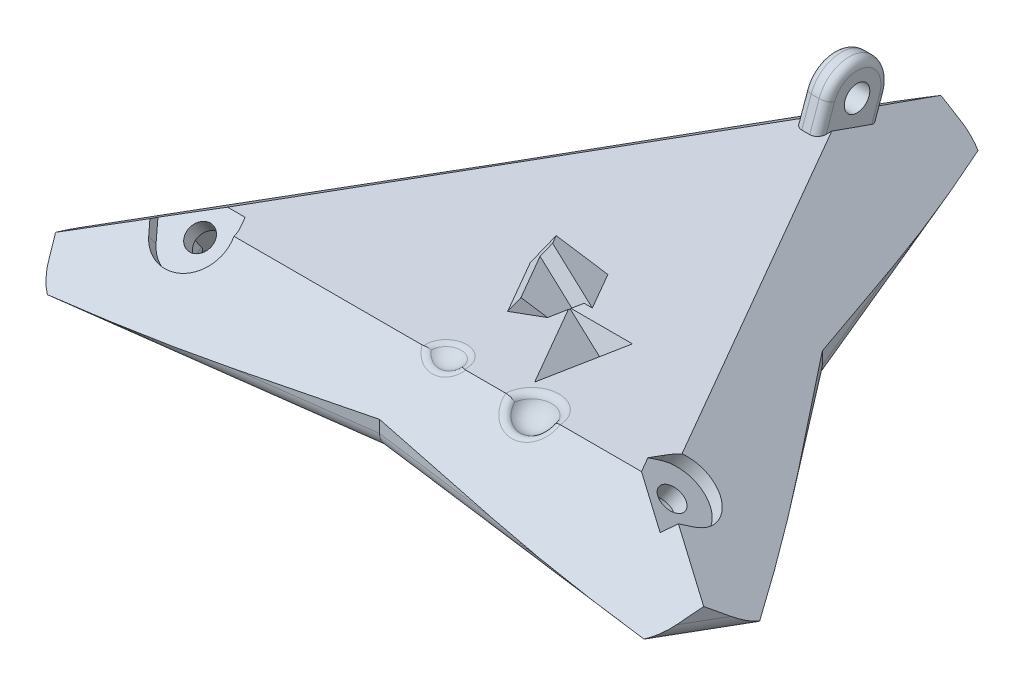
SolidWorks part; units mm, degrees
ref_plane "Front Plane" through (0, 0, 0) normal (0, 0, 1) x (1, 0, 0)
ref_plane "Top Plane" through (0, 0, 0) normal (0, 1, 0) x (1, 0, 0)
ref_plane "Right Plane" through (0, 0, 0) normal (1, 0, 0) x (0, 0, -1)
sketch "Sketch2" plane through (0, 0, 0) normal (0, 1, 0) x (1, 0, 0)
  line L0 (0, 57.735) -> (-50, -28.8675)
  line L1 (-50, -28.8675) -> (50, -28.8675)
  line L2 (50, -28.8675) -> (0, 57.735)
  line L3 (0, 0) -> (0, 57.735) construction
  line L4 (50, -28.8675) -> (0, 0) construction
  line L5 (0, 0) -> (-50, -28.8675) construction
  line L6 (0, 0) -> (0, -28.8675) construction
  line L7 (0, 0) -> (25, 14.4338) construction
  line L8 (0, 0) -> (-25, 14.4338) construction
  line L9 (10, 40.4145) -> (0, 34.641) construction
  line L10 (0, 34.641) -> (-10, 40.4145) construction
  dimension "D1" = 20
sketch "Sketch3" plane through (0, 0, 0) normal (1, 0, 0) x (0, 0, -1)
  line L0 (-28.8675, 0) -> (-19.245, 27.2166) construction
  line L1 (-19.245, 27.2166) -> (0, 20.4124) construction
  line L2 (0, 20.4124) -> (-28.8675, 0) construction
  line L3 (-19.245, 27.2166) -> (-28.983, -0.3266) construction
  line L4 (-28.983, -0.3266) -> (0.2309, 20.3308)
  line L5 (0.2309, 20.3308) -> (-19.245, 27.2166)
  line L6 (-28.983, -0.3266) -> (-28.983, 27.2166)
  line L7 (-28.983, 27.2166) -> (-19.245, 27.2166)
  line L8 (0, 0) -> (0, 103.8474) construction
  dimension "D1" = 0.2
ref_plane "Plane1" through (0, 0, 0) normal (0.5, 0, 0.866) x (0.866, 0, -0.5)
sketch "Sketch4" plane through (0, 0, 0) normal (0.5, 0, 0.866) x (0.866, 0, -0.5)
  line L0 (0, 20.4124) -> (19.245, 27.2166) construction
  line L1 (19.245, 27.2166) -> (28.8675, 0) construction
  line L2 (28.8675, 0) -> (0, 20.4124) construction
  line L3 (0, 81.6497) -> (0, 0) construction
  line L4 (-0.2309, 20.3308) -> (19.245, 27.2166)
  line L5 (19.245, 27.2166) -> (28.983, -0.3266) construction
  line L6 (28.983, -0.3266) -> (-0.2309, 20.3308)
  line L7 (19.245, 27.2166) -> (28.983, 27.2166)
  line L8 (28.983, 27.2166) -> (28.983, -0.3266)
  dimension "D1" = 0.2
ref_plane "Plane2" through (0, 0, 0) normal (0.5, 0, -0.866) x (-0.866, 0, -0.5)
sketch "Sketch5" plane through (0, 0, 0) normal (0.5, 0, -0.866) x (-0.866, 0, -0.5)
  line L0 (19.245, 27.2166) -> (0, 20.4124) construction
  line L1 (0, 20.4124) -> (28.8675, 0) construction
  line L2 (28.8675, 0) -> (19.245, 27.2166) construction
  line L3 (19.245, 27.2166) -> (-0.2309, 20.3308)
  line L4 (-0.2309, 20.3308) -> (28.983, -0.3266)
  line L5 (28.983, -0.3266) -> (19.245, 27.2166) construction
  line L6 (19.245, 27.2166) -> (28.983, 27.2166)
  line L7 (28.983, 27.2166) -> (28.983, -0.3266)
  dimension "D1" = 0.2
extrude "Boss-Extrude1" add sketch "Sketch2" along normal up to vertex (20.4124 mm away) up to point (0, 20.4124, 0)
extrude "Cut-Extrude2" cut sketch "Sketch3" against normal up to vertex (50 mm away) from vertex at 50 starting at point (50, 0, 28.8675)
extrude "Cut-Extrude3" cut sketch "Sketch4" along normal through all and the other way through all
extrude "Cut-Extrude4" cut sketch "Sketch5" along normal through all from vertex at -50 starting at point (-50, 0, 28.8675)
sketch "Sketch6" plane through (0, 0, 0) normal (0, 1, 0) x (1, 0, 0)
  line L0 (0, 0) -> (40.7397, -23.5211) construction
  line L1 (0, 0) -> (-40.7397, -23.5211) construction
  line L2 (0, 0) -> (0, -23.5211) construction
  line L3 (0, 0) -> (0, 47.0422) construction
  line L4 (0, 0) -> (-20.3699, 11.7606) construction
  line L5 (0, 0) -> (20.3699, 11.7606) construction
  line L6 (0, 0) -> (25, 14.4338) construction
  line L7 (50, -28.8675) -> (0, 0) construction
  line L8 (49.4, -28.5211) -> (0, 57.0422) construction
  line L9 (40.7397, -23.5211) -> (37.853, -28.5211) construction
  line L10 (0, 57.0422) -> (-49.4, -28.5211) construction
  line L11 (-49.4, -28.5211) -> (49.4, -28.5211) construction
  line L12 (37.853, -28.5211) -> (0, -23.5211)
  line L13 (0, -23.5211) -> (-37.853, -28.5211)
  line L14 (-37.853, -28.5211) -> (-40.7397, -23.5211) construction
  line L15 (-40.7397, -23.5211) -> (-43.6265, -18.5211) construction
  line L16 (-43.6265, -18.5211) -> (-20.3699, 11.7606)
  line L18 (5.7735, 47.0422) -> (-5.7735, 47.0422)
  line L19 (-37.853, -28.5211) -> (-43.6265, -18.5211)
  line L21 (20.3699, 11.7606) -> (43.6265, -18.5211)
  line L22 (43.6265, -18.5211) -> (40.7397, -23.5211) construction
  line L23 (0, 57.0422) -> (49.4, -28.5211) construction
  line L24 (0, 0) -> (0, 57.735) construction
  line L27 (43.6265, -18.5211) -> (37.853, -28.5211)
  line L35 (50, -28.8675) -> (0, 57.735) construction
  line L36 (50, -28.8675) -> (0, 57.735) construction
  line L37 (0, 57.735) -> (-50, -28.8675) construction
  line L38 (0, 57.735) -> (-50, -28.8675) construction
  line L46 (20.3699, 11.7606) -> (5.7735, 47.0422)
  line L47 (-5.7735, 47.0422) -> (-20.3699, 11.7606)
  circle A0 centre (0, 0) radius 47.0422 construction
  circle A1 centre (0, 0) radius 23.5211 construction
  circle A2 centre (0, 0) radius 57.0422 construction
  dimension "D1" = 10
  dimension "D2" = 5
extrude "Cut-Extrude5" cut sketch "Sketch6" along normal through all flip side to cut
sketch "Sketch7" plane through (0, 0, 0) normal (1, 0, 0) x (0, 0, -1)
  line L0 (31.2288, 11.3333) -> (27.2218, 0) construction
  line L1 (35.7071, 0) -> (27.2218, 0) construction
  line L2 (38.7712, 8.6667) -> (35.7071, 0) construction
  line L3 (31.2288, 11.3333) -> (27.2218, 0)
  line L4 (35.7071, 0) -> (27.2218, 0)
  line L5 (38.7712, 8.6667) -> (35.7071, 0)
  arc A0 (38.7712, 8.6667) -> (31.2288, 11.3333) centre (35, 10) ccw construction
  arc A1 (38.7712, 8.6667) -> (31.2288, 11.3333) centre (35, 10) ccw
  circle A2 centre (35, 10) radius 1.6 construction
  circle A3 centre (35, 10) radius 1.6 construction
  circle A4 centre (35, 10) radius 4 construction
  circle A5 centre (35, 10) radius 4 construction
sketch "Sketch8" plane through (0, 0, 0) normal (0, 1, 0) x (1, 0, 0)
  line L0 (0, 27.2218) -> (0, 35.7071) construction
  line L1 (-1.5, 27.2218) -> (1.5, 27.2218)
  line L2 (-1.5, 27.2218) -> (-1.5, 35.7071)
  line L3 (-1.5, 35.7071) -> (1.5, 35.7071)
  line L4 (1.5, 27.2218) -> (1.5, 35.7071)
  line L5 (0, 31.4645) -> (-1.5, 31.4645) construction
  line L6 (0, 31.4645) -> (1.5, 31.4645) construction
  line L7 (3.7, 27.2218) -> (3.9, 27.2218) construction
  line L8 (1.8, 27.2218) -> (3.7, 27.2218)
  line L9 (1.8, 27.2218) -> (1.8, 35.7071)
  line L10 (1.8, 35.7071) -> (3.7, 35.7071)
  line L11 (3.7, 27.2218) -> (3.7, 35.7071)
  line L12 (-1.8, 27.2218) -> (-3.7, 27.2218)
  line L13 (-1.8, 27.2218) -> (-1.8, 35.7071)
  line L14 (-1.8, 35.7071) -> (-3.7, 35.7071)
  line L15 (-3.7, 27.2218) -> (-3.7, 35.7071)
  line L16 (3.9, 27.2218) -> (3.9, 35.7071) construction
  line L17 (3.9, 35.7071) -> (3.7, 35.7071) construction
  line L18 (-3.7, 35.7071) -> (-3.9, 35.7071) construction
  line L19 (-3.9, 35.7071) -> (-3.9, 27.2218) construction
  line L20 (-3.9, 27.2218) -> (-3.7, 27.2218) construction
  line L21 (-1.8, 27.2218) -> (-1.5, 27.2218) construction
  line L22 (1.8, 27.2218) -> (1.5, 27.2218) construction
  line L23 (-1.8, 35.7071) -> (-1.5, 35.7071) construction
  line L24 (1.5, 35.7071) -> (1.8, 35.7071) construction
  dimension "D1" = 3
  dimension "D2" = 0.3
  dimension "D3" = 0.2
  dimension "D4" = 1.9
ref_plane "Plane3" through (0, 8, 0) normal (0, 1, 0) x (1, 0, 0)
sketch "Sketch10" plane through (0, 8, 0) normal (0, 1, 0) x (1, 0, 0)
  circle A0 centre (0, 0) radius 57.0422 construction
  circle A1 centre (0, 0) radius 57.0422
extrude "Cut-Extrude7" cut sketch "Sketch10" along normal through all
extrude "Boss-Extrude2" add sketch "Sketch7" along normal up to vertex (1.5 mm away) and the other way up to vertex (1.5 mm away) up to point (1.5, 0, -35.7071) other way up to point (-1.5, 0, -35.7071)
sketch "Sketch9" plane through (0, 0, 0) normal (1, 0, 0) x (0, 0, -1)
  circle A0 centre (35, 10) radius 1.6 construction
  circle A1 centre (35, 10) radius 1.6
extrude "Cut-Extrude6" cut sketch "Sketch9" against normal through all and the other way through all
fillet "Fillet1" radius 2 9 edges at (40.7397, 0, 23.5211) (18.9265, 0, 26.0211) (-18.9265, 0, 26.0211) (-40.7397, 0, 23.5211) (-31.9982, 0, 3.3803) (-13.0717, 0, -29.4014) (0, 0, -47.0422) (31.9982, 0, 3.3803) (13.0717, 0, -29.4014)
fillet "Fillet2" radius 1 6 edges at (-1.5, 7.2776, -38.2801) (-1.5, 9.6667, -30.6395) (1.5, 7.2776, -38.2801) (1.5, 9.6667, -30.6395) (-1.5, 13.7712, -36.3333) (1.5, 13.7712, -36.3333)
ref_plane "Plane7" through (3.7, 0, 0) normal (1, 0, 0) x (0, 0, -1)
sketch "Sketch15" plane through (3.7, 0, 0) normal (1, 0, 0) x (0, 0, -1)
  circle A1 centre (35, 10) radius 2.85 construction
  circle A2 centre (35, 10) radius 2.85 construction
  circle A3 centre (35, 10) radius 3.15
  dimension "D1" = 0.3
ref_plane "Plane8" through (-3.7, 0, 0) normal (1, 0, 0) x (0, 0, -1)
sketch "Sketch16" plane through (-3.7, 0, 0) normal (1, 0, 0) x (0, 0, -1)
  line L0 (33.2391, 13.05) -> (31.4782, 10)
  line L1 (31.4782, 10) -> (33.2391, 6.95)
  line L2 (33.2391, 6.95) -> (36.7609, 6.95)
  line L3 (36.7609, 6.95) -> (38.5218, 10)
  line L4 (38.5218, 10) -> (36.7609, 13.05)
  line L5 (36.7609, 13.05) -> (33.2391, 13.05)
  line L6 (38.1754, 10) -> (36.5877, 12.75)
  line L7 (36.5877, 12.75) -> (33.4123, 12.75)
  line L8 (33.4123, 12.75) -> (31.8246, 10)
  line L9 (31.8246, 10) -> (33.4123, 7.25)
  line L10 (33.4123, 7.25) -> (36.5877, 7.25)
  line L11 (36.5877, 7.25) -> (38.1754, 10)
  line L12 (38.1754, 10) -> (36.5877, 12.75) construction
  line L13 (36.5877, 12.75) -> (33.4123, 12.75) construction
  line L14 (33.4123, 12.75) -> (31.8246, 10) construction
  line L15 (31.8246, 10) -> (33.4123, 7.25) construction
  line L16 (33.4123, 7.25) -> (36.5877, 7.25) construction
  line L17 (36.5877, 7.25) -> (38.1754, 10) construction
  dimension "D1" = 0
  dimension "D2" = 0.3
sketch "Sketch17" plane through (0, 8, 0) normal (0, 1, 0) x (1, 0, 0)
  line L0 (-10, 10.75) -> (-10, 20.75) construction
  line L1 (10, 20.75) -> (-10, 20.75) construction
  line L2 (10, 10.75) -> (10, 20.75) construction
  line L3 (10, 10.75) -> (-10, 10.75) construction
  line L4 (-10, 10.75) -> (-10, 20.75)
  line L5 (10, 20.75) -> (-10, 20.75)
  line L6 (10, 10.75) -> (10, 20.75)
  line L7 (10, 10.75) -> (-10, 10.75)
  line L8 (-13.75, -9.8438) -> (-13.75, 10.1562) construction
  line L9 (-13.75, 10.1562) -> (-3.75, 10.1562) construction
  line L10 (-3.75, -9.8438) -> (-3.75, 10.1562) construction
  line L11 (-13.75, -9.8438) -> (-3.75, -9.8438) construction
  line L12 (-13.75, -9.8438) -> (-13.75, 10.1562)
  line L13 (-13.75, 10.1562) -> (-3.75, 10.1562)
  line L14 (-3.75, -9.8438) -> (-3.75, 10.1562)
  line L15 (-13.75, -9.8438) -> (-3.75, -9.8438)
  line L16 (7, -9.8438) -> (7, 10.1562) construction
  line L17 (-3, 10.1562) -> (7, 10.1562) construction
  line L18 (-3, -9.8438) -> (-3, 10.1562) construction
  line L19 (-3, -9.8438) -> (7, -9.8438) construction
  line L20 (7, -9.8438) -> (7, 10.1562)
  line L21 (-3, 10.1562) -> (7, 10.1562)
  line L22 (-3, -9.8438) -> (-3, 10.1562)
  line L23 (-3, -9.8438) -> (7, -9.8438)
  line L25 (12.75, 10.1562) -> (7.75, 10.1562)
  line L26 (12.75, 10.1562) -> (12.75, -9.8438)
  line L27 (12.75, -9.8438) -> (7.75, -9.8438)
  line L28 (7.75, 10.1562) -> (7.75, -9.8438)
  line L29 (10, -10.25) -> (-10, -10.25)
  line L30 (10, -10.25) -> (10, -15.25)
  line L31 (10, -15.25) -> (-10, -15.25)
  line L32 (-10, -10.25) -> (-10, -15.25)
sketch "Sketch18" plane through (0, 27.2166, 19.245) normal (0.5, 0.8165, -0.2887) x (0.866, -0.4714, 0.1667)
  line L0 (35.9192, -0.3) -> (39.0541, 8.5667)
  line L1 (30.9459, 11.4333) -> (26.7976, -0.3)
  line L2 (26.7976, -0.3) -> (35.9192, -0.3)
  line L3 (31.2288, 11.3333) -> (27.2218, 0)
  line L4 (27.2218, 0) -> (35.7071, 0)
  line L5 (35.7071, 0) -> (38.7712, 8.6667)
  line L6 (31.2288, 11.3333) -> (27.2218, 0) construction
  line L7 (27.2218, 0) -> (35.7071, 0) construction
  line L8 (35.7071, 0) -> (38.7712, 8.6667) construction
  arc A0 (39.0541, 8.5667) -> (30.9459, 11.4333) centre (35, 10) ccw
  arc A1 (38.7712, 8.6667) -> (31.2288, 11.3333) centre (35, 10) ccw
  arc A2 (38.7712, 8.6667) -> (31.2288, 11.3333) centre (35, 10) ccw construction
  dimension "D1" = 0
  dimension "D2" = 0.3
extrude "Cut-Extrude8" cut sketch "Sketch18" against normal up to vertex (1.8 mm away)
sketch "Sketch19" plane through (0, 27.2166, 19.245) normal (0.5, 0.8165, -0.2887) x (0.866, -0.4714, 0.1667)
  circle A0 centre (35, 10) radius 1.6 construction
  circle A1 centre (35, 10) radius 1.6
extrude "Cut-Extrude9" cut sketch "Sketch19" against normal through all
sketch "Sketch20" plane through (-1.85, 24.1955, 20.3131) normal (0.5, 0.8165, -0.2887) x (0.866, -0.4714, 0.1667)
  line L6 (33.2391, 13.05) -> (31.4782, 10)
  line L7 (31.4782, 10) -> (33.2391, 6.95)
  line L8 (33.2391, 6.95) -> (36.7609, 6.95)
  line L9 (36.7609, 6.95) -> (38.5218, 10)
  line L10 (38.5218, 10) -> (36.7609, 13.05)
  line L11 (36.7609, 13.05) -> (33.2391, 13.05)
  line L12 (33.2391, 13.05) -> (31.4782, 10) construction
  line L13 (31.4782, 10) -> (33.2391, 6.95) construction
  line L14 (33.2391, 6.95) -> (36.7609, 6.95) construction
  line L15 (36.7609, 6.95) -> (38.5218, 10) construction
  line L16 (38.5218, 10) -> (36.7609, 13.05) construction
  line L17 (36.7609, 13.05) -> (33.2391, 13.05) construction
  circle A1 centre (35, 10) radius 3.15
  circle A2 centre (35, 10) radius 3.15
  dimension "D1" = 0
  dimension "D2" = 0
extrude "Cut-Extrude10" cut sketch "Sketch20" against normal through all
sketch "Sketch21" plane through (-16.6667, 27.2166, -9.6225) normal (0, 0.8165, 0.5774) x (-0.5774, -0.4714, 0.6667)
  line L0 (30.9459, 11.4333) -> (26.7976, -0.3)
  line L1 (26.7976, -0.3) -> (35.9192, -0.3)
  line L2 (35.9192, -0.3) -> (39.0541, 8.5667)
  line L3 (31.2288, 11.3333) -> (27.2218, 0)
  line L4 (27.2218, 0) -> (35.7071, 0)
  line L5 (35.7071, 0) -> (38.7712, 8.6667)
  line L6 (31.2288, 11.3333) -> (27.2218, 0) construction
  line L7 (27.2218, 0) -> (35.7071, 0) construction
  line L8 (35.7071, 0) -> (38.7712, 8.6667) construction
  arc A0 (39.0541, 8.5667) -> (30.9459, 11.4333) centre (35, 10) ccw
  arc A1 (38.7712, 8.6667) -> (31.2288, 11.3333) centre (35, 10) ccw
  arc A2 (38.7712, 8.6667) -> (31.2288, 11.3333) centre (35, 10) ccw construction
  dimension "D1" = 0
  dimension "D2" = 0.3
extrude "Cut-Extrude11" cut sketch "Sketch21" against normal up to vertex (1.8 mm away)
sketch "Sketch22" plane through (-16.6667, 24.1955, -11.7587) normal (0, 0.8165, 0.5774) x (-0.5774, -0.4714, 0.6667)
  line L6 (33.2391, 13.05) -> (31.4782, 10)
  line L7 (31.4782, 10) -> (33.2391, 6.95)
  line L8 (33.2391, 6.95) -> (36.7609, 6.95)
  line L9 (36.7609, 6.95) -> (38.5218, 10)
  line L10 (38.5218, 10) -> (36.7609, 13.05)
  line L11 (36.7609, 13.05) -> (33.2391, 13.05)
  line L12 (33.2391, 13.05) -> (31.4782, 10)
  line L13 (31.4782, 10) -> (33.2391, 6.95)
  line L14 (33.2391, 6.95) -> (36.7609, 6.95)
  line L15 (36.7609, 6.95) -> (38.5218, 10)
  line L16 (38.5218, 10) -> (36.7609, 13.05)
  line L17 (36.7609, 13.05) -> (33.2391, 13.05)
  dimension "D1" = 0
extrude "Cut-Extrude12" cut sketch "Sketch22" against normal through all
sketch "Sketch23" plane through (-16.6667, 27.2166, -9.6225) normal (0, 0.8165, 0.5774) x (-0.5774, -0.4714, 0.6667)
  circle A0 centre (35, 10) radius 1.6 construction
  circle A1 centre (35, 10) radius 1.6
extrude "Cut-Extrude13" cut sketch "Sketch23" against normal through all
ref_plane "Plane9" through (3.3333, 5.4433, -1.9245) normal (-0.5, -0.8165, 0.2887) x (-0.866, 0.4714, -0.1667)
sketch "Sketch24" plane through (3.3333, 5.4433, -1.9245) normal (-0.5, -0.8165, 0.2887) x (-0.866, 0.4714, -0.1667)
  line L0 (-0.6899, -5.5166) -> (17.6225, -5.5166) construction
  line L2 (17.6225, -5.5166) -> (17.6225, -19.2166) construction
  line L3 (-0.6899, -5.5166) -> (17.6225, -5.5166) construction
  line L4 (-0.6899, -19.2166) -> (17.6225, -19.2166)
  line L5 (17.6225, -5.5166) -> (17.6225, -19.2166) construction
  line L6 (-0.6899, -19.2166) -> (-0.6899, -5.5166) construction
  line L7 (-0.6899, -19.2166) -> (-0.6899, -5.5166) construction
  line L8 (17.6225, -19.2166) -> (17.6225, -5.0166)
  line L9 (17.6225, -5.0166) -> (-0.6899, -5.0166)
  line L10 (-0.6899, -5.0166) -> (-0.6899, -19.2166)
  dimension "D1" = 0.5
extrude "Cut-Extrude14" cut sketch "Sketch24" against normal through all
ref_plane "Plane10" through (6.3891, -3.4778, 1.2296) normal (0.866, -0.4714, 0.1667) x (0.1464, -0.0797, -0.986)
sketch "Sketch25" plane through (6.3891, -3.4778, 1.2296) normal (0.866, -0.4714, 0.1667) x (0.1464, -0.0797, -0.986)
  line L0 (-3.8409, 9.0307) -> (1.5204, 26.5407) construction
  line L1 (1.5204, 26.5407) -> (-10.8144, 30.3174) construction
  line L2 (-16.1757, 12.8074) -> (-3.8409, 9.0307) construction
  line L3 (-3.8409, 9.0307) -> (1.5204, 26.5407)
  line L4 (1.5204, 26.5407) -> (-10.8144, 30.3174)
  line L5 (-16.1757, 12.8074) -> (-3.8409, 9.0307)
  line L6 (-10.8144, 30.3174) -> (-16.1757, 12.8074)
extrude "Cut-Extrude15" cut sketch "Sketch25" against normal through all
sketch "Sketch26" plane through (3.3333, 5.4433, -1.9245) normal (0.5, 0.8165, -0.2887) x (0.866, -0.4714, 0.1667)
  line L0 (0.6899, -5.5166) -> (-5.197, -5.5166) construction
  line L1 (-5.197, -5.5166) -> (0.6899, -13.8419) construction
  line L2 (0.6899, -13.8419) -> (0.6899, -5.5166) construction
  line L3 (0.6899, -8.6457) -> (-1.8763, -5.0166) construction
  line L4 (0.6899, -8.6457) -> (-1.8763, -5.0166) construction
  line L5 (-1.7596, -10.3778) -> (-6.2577, -4.0166)
  line L6 (0.6899, -5.0166) -> (0.6899, -19.2166) construction
  line L7 (0.6899, -8.6457) -> (0.6899, 0.8961)
  line L8 (-6.2577, -4.0166) -> (0.6899, 0.8961)
  line L9 (0.6899, -5.0166) -> (-5.5506, -5.0166) construction
  line L10 (-17.6225, -5.0166) -> (0.6899, -5.0166) construction
  line L11 (0.6899, -5.5166) -> (-17.6225, -5.5166) construction
  line L12 (0.6899, -8.6457) -> (-1.7596, -10.3778)
  dimension "D1" = 3
  dimension "D3" = 1
extrude "Boss-Extrude3" add sketch "Sketch26" against normal up to surface
sketch "Sketch27" plane through (3.3333, 5.4433, -1.9245) normal (0.5, 0.8165, -0.2887) x (0.866, -0.4714, 0.1667)
  line L0 (0.6899, -5.0166) -> (-5.5506, -5.0166) construction
  line L2 (-6.2577, -4.0166) -> (0.6899, 0.8961) construction
  line L3 (-1.7596, -10.3778) -> (-6.2577, -4.0166) construction
  line L4 (0.6899, -5.0166) -> (-5.5506, -5.0166) construction
  line L5 (0.6899, -5.0166) -> (0.6899, 0.8961) construction
  line L6 (-6.2577, -4.0166) -> (0.6899, 0.8961)
  line L7 (-5.5506, -5.0166) -> (-6.2577, -4.0166)
  line L8 (-5.5506, -5.0166) -> (4.1036, -5.0166)
  line L9 (4.1036, -5.0166) -> (0.6899, 0.8961)
  line L10 (0.6899, -8.6457) -> (0.6899, 0.8961) construction
  dimension "D1" = 60
extrude "Boss-Extrude4" add sketch "Sketch27" along normal up to surface (2 mm away)
sketch "Sketch28" plane through (0, 6.4055, 18.1175) normal (0, -0.3333, -0.9428) x (-1, 0, 0)
  line L0 (0.974, 3.5087) -> (-4.526, 3.5087)
  arc A0 (-4.526, 3.5087) -> (0.974, 3.5087) centre (-1.776, 3.5087) ccw
  circle A1 centre (-1.776, 3.5087) radius 0.75 construction
  ellipse E1 centre (-1.776, 3.5087) end of major axis (-1.271, 2.6341) minor radius 0.75 (-2.4255, 3.1337) -> (-1.1264, 3.8837) ccw construction
  dimension "D1" = 2
revolve "Cut-Revolve1" cut sketch "Sketch28" angle 360 about L0
sketch "Sketch29" plane through (0, 6.4055, 18.1175) normal (0, -0.3333, -0.9428) x (-1, 0, 0)
  line L0 (-10.2204, 2.2303) -> (-15.7204, 2.2303)
  circle A0 centre (-12.9704, 2.2303) radius 0.75 construction
  arc A1 (-15.7204, 2.2303) -> (-10.2204, 2.2303) centre (-12.9704, 2.2303) ccw
  ellipse E0 centre (-12.9704, 2.2303) end of major axis (-12.0958, 2.7352) minor radius 0.75 (-13.3454, 2.8798) -> (-13.9218, 2.0376) ccw construction
  dimension "D1" = 2
revolve "Cut-Revolve2" cut sketch "Sketch29" angle 360 about L0
fillet "Fillet3" radius 1 4 edges at (1.776, 8, 14.7971) (1.776, 7.2791, 18.227) (12.9704, 8, 14.6715) (12.9704, 6.5308, 19.2852)
fillet "Fillet4" radius 1 7 edges at (-28.9888, 0, 16.9233) (-26.2186, 0, 15.3602) (-25.9388, 0, 11.6405) (-28.4291, 0, 9.4838) (-31.1993, 0, 11.0469) (-31.4791, 0, 14.7666) (29.1302, 0, 16.3319)
